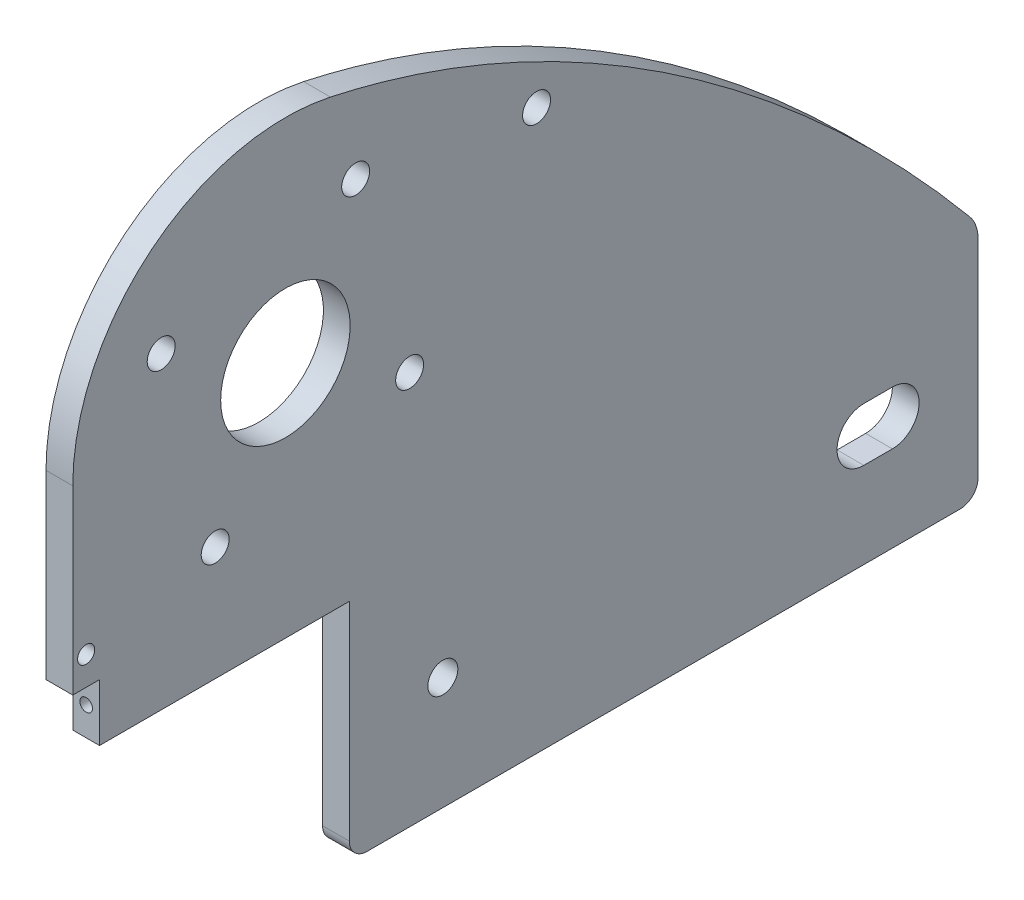
SolidWorks part; units mm, degrees
ref_plane "Front Plane" through (0, 0, 0) normal (0, 0, 1) x (1, 0, 0)
ref_plane "Top Plane" through (0, 0, 0) normal (0, 1, 0) x (1, 0, 0)
ref_plane "Right Plane" through (0, 0, 0) normal (1, 0, 0) x (0, 0, -1)
sketch "Sketch1" plane through (0, 0, 0) normal (1, 0, 0) x (0, 0, -1)
  line L0 (-28.1703, 0) -> (77.3828, 0)
  line L1 (80.5578, 3.175) -> (80.5578, 40.132)
  line L2 (-80.5578, 82.55) -> (-80.5578, 50.292)
  line L4 (-75.7953, 50.292) -> (-75.7953, 40.132)
  line L5 (-80.5578, 50.292) -> (-75.7953, 50.292)
  line L6 (65.3178, 20.066) -> (60.2378, 20.066) construction
  line L7 (-75.7953, 40.132) -> (-31.3453, 40.132)
  line L10 (-31.3453, 40.132) -> (-31.3453, 3.175)
  line L11 (-37.7935, 96.5728) -> (77.9184, 56.022) construction
  line L12 (-52.4128, 71.2982) -> (40.4331, -8.7847) construction
  line L13 (65.3178, 15.3035) -> (60.2378, 15.3035)
  line L14 (65.3178, 24.8285) -> (60.2378, 24.8285)
  arc A0 (65.3178, 15.3035) -> (65.3178, 24.8285) centre (65.3178, 20.066) ccw
  circle A1 centre (-42.7078, 82.55) radius 31.5 construction
  circle A2 centre (65.3178, 20.066) radius 76.2 construction
  circle A3 centre (65.3178, 20.066) radius 38.1 construction
  circle A4 centre (-42.7078, 82.55) radius 14.859 construction
  arc A5 (-34.6964, 119.5424) -> (-80.5578, 82.55) centre (-42.7078, 82.55) ccw
  arc A6 (-28.1703, 0) -> (-31.3453, 3.175) centre (-28.1703, 3.175) cw
  arc A7 (77.3828, 0) -> (80.5578, 3.175) centre (77.3828, 3.175) ccw
  arc A8 (80.5578, 40.132) -> (79.0888, 44.1938) centre (74.2078, 40.132) ccw
  circle A9 centre (1.9922, 99.567) radius 6.35 construction
  circle A10 centre (-55.209, 60.4394) radius 2.4892
  circle A11 centre (-14.6922, 20.066) radius 2.667
  circle A12 centre (-20.5972, 70.0488) radius 2.4892
  circle A13 centre (-64.8184, 95.0512) radius 2.4892
  circle A14 centre (-30.2065, 104.6606) radius 2.4892
  circle A15 centre (-78.1765, 55.372) radius 1.524
  circle A16 centre (-42.7078, 82.55) radius 11.5228
  arc A17 (60.2378, 24.8285) -> (60.2378, 15.3035) centre (60.2378, 20.066) ccw
  circle A19 centre (1.9922, 99.567) radius 2.4892
  spline S0 degree 3 poles (79.0888, 44.1938) (50.6675, 78.3472) (10.808, 109.6876) (-34.6964, 119.5424) knots 0 0 0 0 1 1 1 1
  point P28 (80.5578, 40.132)
  point P39 (62.7778, 20.066)
  dimension "D4" = 9.525
  dimension "D7" = 29.718
  dimension "D8" = 63
  dimension "D9" = 6.35
  dimension "D12" = 3.175
  dimension "D13" = 6.35
  dimension "D14" = 76.2
  dimension "D15" = 152.4
  dimension "D18" = 5.334
  dimension "D19" = 4.9784
  dimension "D23" = 3.048
  dimension "D27" = 82.55
  dimension "D28" = 12.7
  dimension "D29" = 4.9784
  dimension "D2" = 40.132
  dimension "D3" = 20.066
  dimension "D5" = 15.24
  dimension "D6" = 44.45
  dimension "D10" = 161.1156
  dimension "D11" = 95.25
  dimension "D17" = 25.4
  dimension "D21" = 4.7625
  dimension "D22" = 10.16
  dimension "D24" = 5.08
  dimension "D25" = 2.3813
  dimension "D26" = 5.08
  dimension "D16" = 4
extrude "Boss-Extrude1" add sketch "Sketch1" along normal blind 4.7625
sketch "Sketch2" plane through (0, 0, 75.7953) normal (0, 0, 1) x (1, 0, 0)
  line L0 (4.7625, 50.292) -> (4.7625, 40.132) construction
  line L1 (4.7625, 40.132) -> (0, 40.132) construction
  circle A0 centre (2.3813, 45.212) radius 1.1303
  point P4 (4.7625, 45.212)
  point P7 (2.3813, 40.132)
  dimension "D1" = 2.2606
extrude "Cut-Extrude1" cut sketch "Sketch2" against normal blind 6.35
